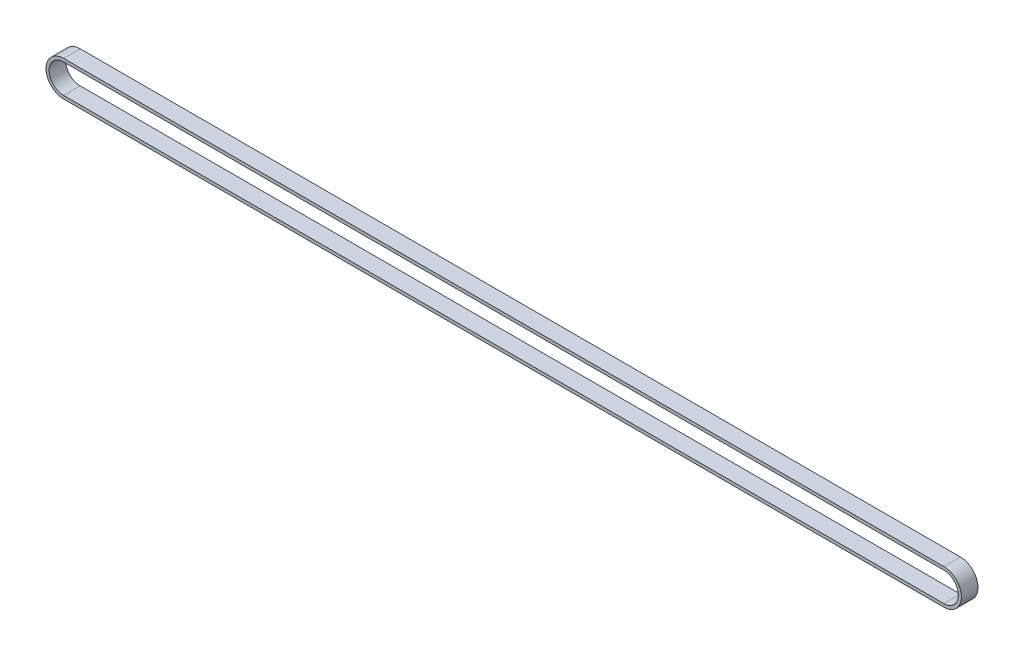
SolidWorks part; units mm, degrees
material "PF"
ref_plane "Piano frontale" through (0, 0, 0) normal (0, 0, 1) x (1, 0, 0)
ref_plane "Piano superiore" through (0, 0, 0) normal (0, 1, 0) x (1, 0, 0)
ref_plane "Piano destro" through (0, 0, 0) normal (1, 0, 0) x (0, 0, -1)
sketch "Schizzo1" plane through (0, 0, 0) normal (0, 0, 1) x (1, 0, 0)
  line L0 (0, 0) -> (-340, 0) construction
  line L1 (0, -5.6) -> (-340, -5.6)
  line L2 (0, 5.6) -> (-340, 5.6)
  line L3 (0, 0) -> (-340, 0) construction
  line L4 (0, -6.8) -> (-340, -6.8)
  line L5 (0, 6.8) -> (-340, 6.8)
  arc A0 (0, -5.6) -> (0, 5.6) centre (0, 0) ccw
  arc A1 (-340, 5.6) -> (-340, -5.6) centre (-340, 0) ccw
  arc A2 (0, -6.8) -> (0, 6.8) centre (0, 0) ccw
  arc A3 (-340, 6.8) -> (-340, -6.8) centre (-340, 0) ccw
  point P3 (-170, 0)
  point P8 (-170, 0)
  dimension "D3" = 5.6
  dimension "D1" = 1.2
  dimension "D2" = 340
extrude "Estrusione-Estrusione1" add sketch "Schizzo1" along normal blind 6.4
